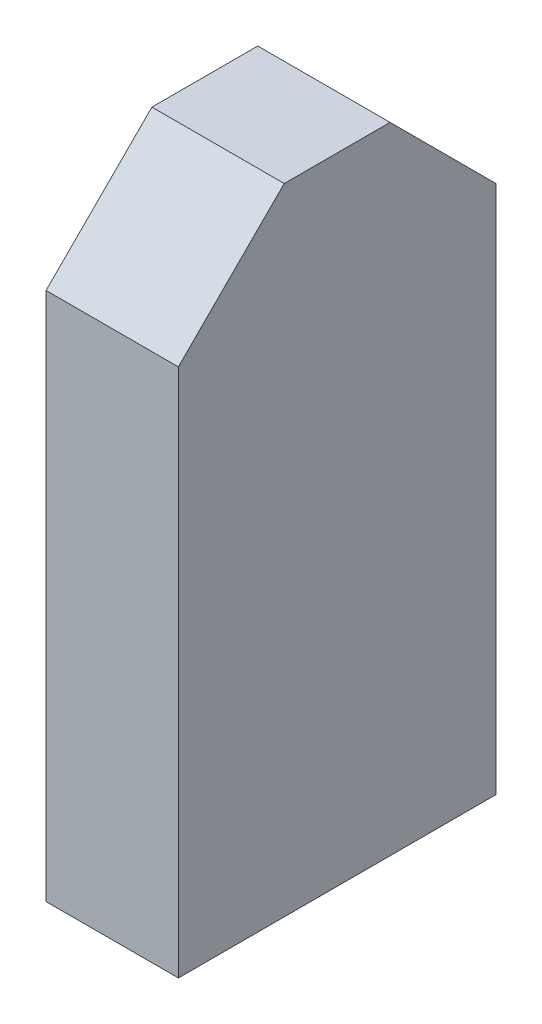
SolidWorks part; units mm, degrees
ref_plane "Front Plane" through (0, 0, 0) normal (0, 0, 1) x (1, 0, 0)
ref_plane "Top Plane" through (0, 0, 0) normal (0, 1, 0) x (1, 0, 0)
ref_plane "Right Plane" through (0, 0, 0) normal (1, 0, 0) x (0, 0, -1)
sketch "Sketch1" plane through (0, 0, 0) normal (1, 0, 0) x (0, 0, -1)
  line L1 (-19.05, 38.1) -> (19.05, 38.1)
  line L2 (-19.05, 38.1) -> (-19.05, -38.1)
  line L3 (-19.05, -38.1) -> (19.05, -38.1)
  line L4 (19.05, 38.1) -> (19.05, -38.1)
  line L5 (-19.05, 38.1) -> (19.05, -38.1) construction
  line L6 (-19.05, -38.1) -> (19.05, 38.1) construction
  point P0 (0, 0)
  dimension "D1" = 38.1
  dimension "D2" = 76.2
extrude "Boss-Extrude1" add sketch "Sketch1" along normal blind 15.875
chamfer "Chamfer1" distance 12.7 angle 45 2 edges at (7.9375, 38.1, -19.05) (7.9375, 38.1, 19.05)
